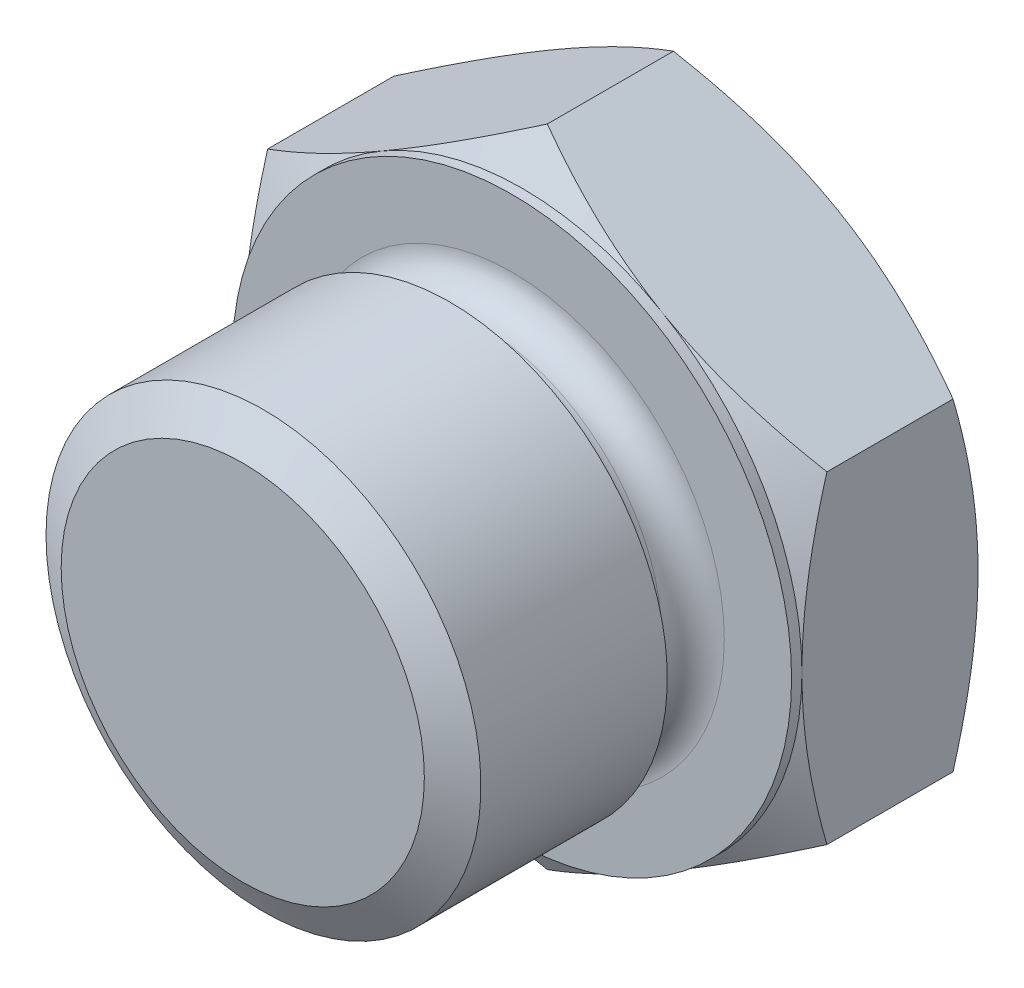
SolidWorks part; units mm, degrees
ref_plane "Plan1" through (0, 0, 0) normal (0, 0, 1) x (1, 0, 0)
ref_plane "Plan2" through (0, 0, 0) normal (0, 1, 0) x (1, 0, 0)
ref_plane "Plan3" through (0, 0, 0) normal (1, 0, 0) x (0, 0, -1)
sketch "Esquisse1" plane through (0, 0, 0) normal (0, 0, 1) x (1, 0, 0)
  circle A0 centre (0, 0) radius 16
  dimension "D1" = 32
extrude "Base-Extrusion" add sketch "Esquisse1" along normal blind 8.5
chamfer "Chanfrein1" distance 2.5 angle 30 2 edges at (16, 0, 0) (16, 0, 8.5)
sketch "Esquisse2" plane through (0, 0, 8.5) normal (0, 0, 1) x (1, 0, 0)
  line L0 (0, 0) -> (19.3649, 11.1803) construction
  line L1 (0, 0) -> (20, 0) construction
  line L2 (13.5, -7.7942) -> (13.5, 7.7942)
  line L3 (0, -15.5885) -> (13.5, -7.7942)
  line L4 (-13.5, -7.7942) -> (0, -15.5885)
  line L5 (-13.5, 7.7942) -> (-13.5, -7.7942)
  line L6 (0, 15.5885) -> (-13.5, 7.7942)
  line L7 (13.5, 7.7942) -> (0, 15.5885)
  point P8 (13.5, 0)
  dimension "D2" = 30
extrude "Enlèv. mat.-Extru.1" cut sketch "Esquisse2" against normal through all flip side to cut
sketch "Esquisse3" plane through (0, 0, 8.5) normal (0, 0, 1) x (1, 0, 0)
  circle A0 centre (0, 0) radius 13.5
extrude "Boss.-Extru.1" add sketch "Esquisse3" along normal blind 0.5
sketch "Esquisse4" plane through (0, 0, 9) normal (0, 0, 1) x (1, 0, 0)
  circle A0 centre (0, 0) radius 10.5
  dimension "D1" = 21
extrude "Boss.-Extru.2" add sketch "Esquisse4" along normal blind 13
cosmetic thread "Représentation de filetage1"
chamfer "Chanfrein2" distance 1 angle 60 1 edges at (10.5, 0, 22)
sketch "Esquisse5" plane through (0, 0, 9) normal (0, 0, 1) x (1, 0, 0)
  circle A0 centre (0, 0) radius 8.75
  dimension "D1" = 17.5
extrude "Enlèv. mat.-Extru.2" cut sketch "Esquisse5" along normal blind 3 flip side to cut
fillet "Congé1" radius 1.5 2 edges at (8.75, 0, 9) (8.75, 0, 12)
